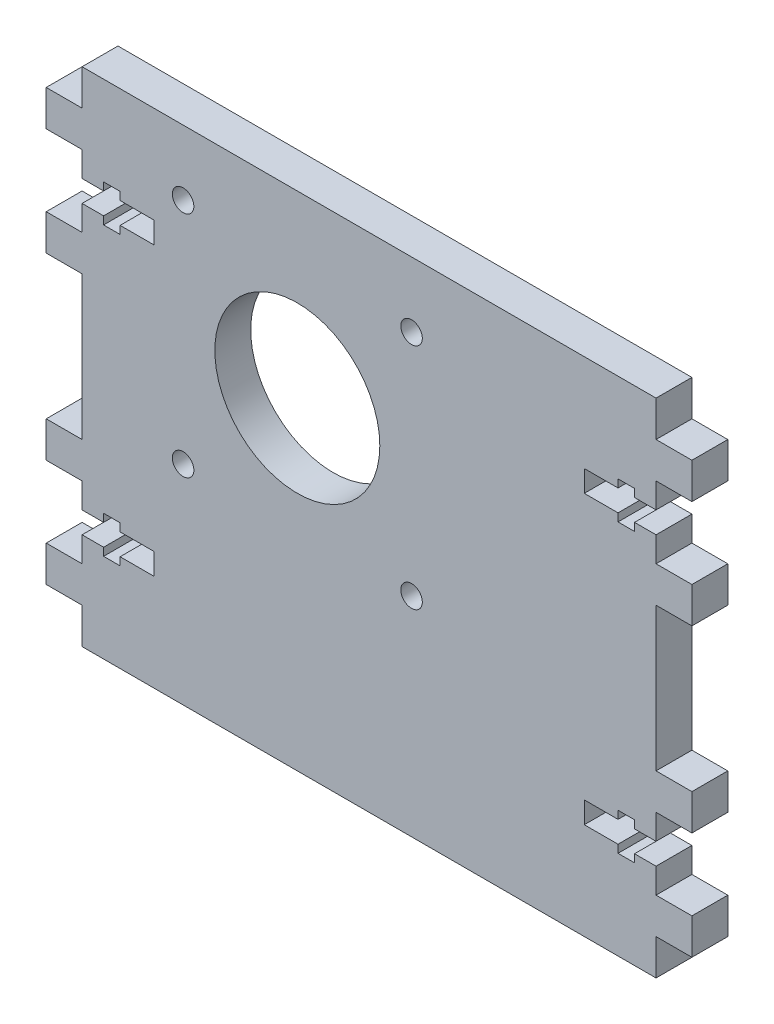
SolidWorks part; units mm, degrees
ref_plane "Front Plane" through (0, 0, 0) normal (0, 0, 1) x (1, 0, 0)
ref_plane "Top Plane" through (0, 0, 0) normal (0, 1, 0) x (1, 0, 0)
ref_plane "Right Plane" through (0, 0, 0) normal (1, 0, 0) x (0, 0, -1)
sketch "Sketch1" plane through (0, 0, 0) normal (0, 0, 1) x (1, 0, 0)
  line L0 (0, 0) -> (0, 70) construction
  line L1 (0, 70) -> (-80, 70)
  line L4 (-40, 38.7693) -> (-40, -40.9046) construction
  line L5 (0, 35) -> (-37.6147, 35) construction
  line L6 (0, 55) -> (-11.2208, 55) construction
  line L7 (0, 53.5) -> (0, 50)
  line L8 (5, 50) -> (5, 45)
  line L9 (5, 45) -> (0, 45)
  line L10 (5, 50) -> (0, 50)
  line L11 (0, 56.5) -> (0, 60)
  line L12 (0, 60) -> (5, 60)
  line L13 (5, 60) -> (5, 65)
  line L14 (5, 65) -> (0, 65)
  line L15 (0, 53.5) -> (0, 56.5) construction
  line L16 (0, 56.5) -> (-3, 56.5)
  line L17 (-5.3, 56.5) -> (-5.3, 57.6)
  line L18 (-3, 52.4) -> (-5.3, 52.4)
  line L19 (-3, 57.6) -> (-3, 56.5)
  line L20 (-5.3, 56.5) -> (-10, 56.5)
  line L21 (-10, 56.5) -> (-10, 53.5)
  line L22 (-10, 53.5) -> (-5.3, 53.5)
  line L23 (-3, 53.5) -> (-3, 52.4)
  line L24 (-5.3, 57.6) -> (-3, 57.6)
  line L25 (-5.3, 52.4) -> (-5.3, 53.5)
  line L26 (-3, 53.5) -> (0, 53.5)
  line L27 (-10, 55) -> (0, 55) construction
  line L66 (-85, 65) -> (-80, 65)
  line L67 (-85, 60) -> (-85, 65)
  line L68 (-80, 60) -> (-85, 60)
  line L69 (-80, 56.5) -> (-80, 60)
  line L70 (-80, 56.5) -> (-77, 56.5)
  line L71 (-77, 57.6) -> (-77, 56.5)
  line L72 (-74.7, 57.6) -> (-77, 57.6)
  line L73 (-74.7, 56.5) -> (-74.7, 57.6)
  line L74 (-74.7, 56.5) -> (-70, 56.5)
  line L75 (-70, 56.5) -> (-70, 53.5)
  line L76 (-70, 53.5) -> (-74.7, 53.5)
  line L77 (-74.7, 52.4) -> (-74.7, 53.5)
  line L78 (-77, 52.4) -> (-74.7, 52.4)
  line L79 (-77, 53.5) -> (-77, 52.4)
  line L80 (-77, 53.5) -> (-80, 53.5)
  line L81 (-80, 53.5) -> (-80, 50)
  line L82 (-85, 50) -> (-80, 50)
  line L83 (-85, 50) -> (-85, 45)
  line L84 (-85, 45) -> (-80, 45)
  line L85 (-80, 70) -> (-80, 65)
  line L90 (0, 65) -> (0, 70)
  line L91 (-85, 25) -> (-80, 25)
  line L92 (-85, 20) -> (-85, 25)
  line L93 (-85, 20) -> (-80, 20)
  line L94 (-80, 16.5) -> (-80, 20)
  line L95 (-77, 16.5) -> (-80, 16.5)
  line L96 (-77, 16.5) -> (-77, 17.6)
  line L97 (-77, 17.6) -> (-74.7, 17.6)
  line L98 (-74.7, 17.6) -> (-74.7, 16.5)
  line L99 (-70, 16.5) -> (-74.7, 16.5)
  line L100 (-70, 13.5) -> (-70, 16.5)
  line L101 (-74.7, 13.5) -> (-70, 13.5)
  line L102 (-74.7, 13.5) -> (-74.7, 12.4)
  line L103 (-74.7, 12.4) -> (-77, 12.4)
  line L104 (-77, 12.4) -> (-77, 13.5)
  line L105 (-80, 13.5) -> (-77, 13.5)
  line L106 (-80, 13.5) -> (-80, 10)
  line L107 (-80, 10) -> (-85, 10)
  line L108 (-85, 10) -> (-85, 5)
  line L109 (-85, 5) -> (-80, 5)
  line L110 (-80, 0) -> (-80, 5)
  line L111 (0, 0) -> (-80, 0)
  line L112 (0, 5) -> (0, 0)
  line L113 (5, 5) -> (0, 5)
  line L114 (5, 10) -> (5, 5)
  line L115 (0, 10) -> (5, 10)
  line L116 (0, 13.5) -> (0, 10)
  line L117 (0, 13.5) -> (-3, 13.5)
  line L118 (-3, 12.4) -> (-3, 13.5)
  line L119 (-5.3, 12.4) -> (-3, 12.4)
  line L120 (-5.3, 13.5) -> (-5.3, 12.4)
  line L121 (-5.3, 13.5) -> (-10, 13.5)
  line L122 (-10, 13.5) -> (-10, 16.5)
  line L123 (-10, 16.5) -> (-5.3, 16.5)
  line L124 (-5.3, 17.6) -> (-5.3, 16.5)
  line L125 (-3, 17.6) -> (-5.3, 17.6)
  line L126 (-3, 16.5) -> (-3, 17.6)
  line L127 (-3, 16.5) -> (0, 16.5)
  line L128 (0, 16.5) -> (0, 20)
  line L129 (5, 20) -> (0, 20)
  line L130 (5, 20) -> (5, 25)
  line L131 (5, 25) -> (0, 25)
  line L132 (-80, 45) -> (-80, 25)
  line L133 (0, 45) -> (0, 25)
  point P7 (-80, 45)
  circle B0 centre (-65.922, 60.922) radius 1.5
  circle B1 centre (-34.078, 60.922) radius 1.5
  circle B2 centre (-34.078, 29.078) radius 1.5
  circle B3 centre (-65.922, 29.078) radius 1.5
  circle B4 centre (-50, 45) radius 11.5
  dimension "D2" = 40
  dimension "D3" = 80
  dimension "D4" = 10
  dimension "D5" = 5
  dimension "D6" = 5
  dimension "D7" = 5.2
  dimension "D8" = 3
  dimension "D9" = 2.3
  dimension "D10" = 3
  dimension "D11" = 10
  dimension "D12" = 70
  dimension "D13" = 15
  dimension "D14" = 50
  dimension "D15" = 10
sketch_block_instance "Fixation Nema 17-1"
sketch_block "Fixation Nema 17"
extrude "Boss-Extrude1" add sketch "Sketch1" along normal blind 5
